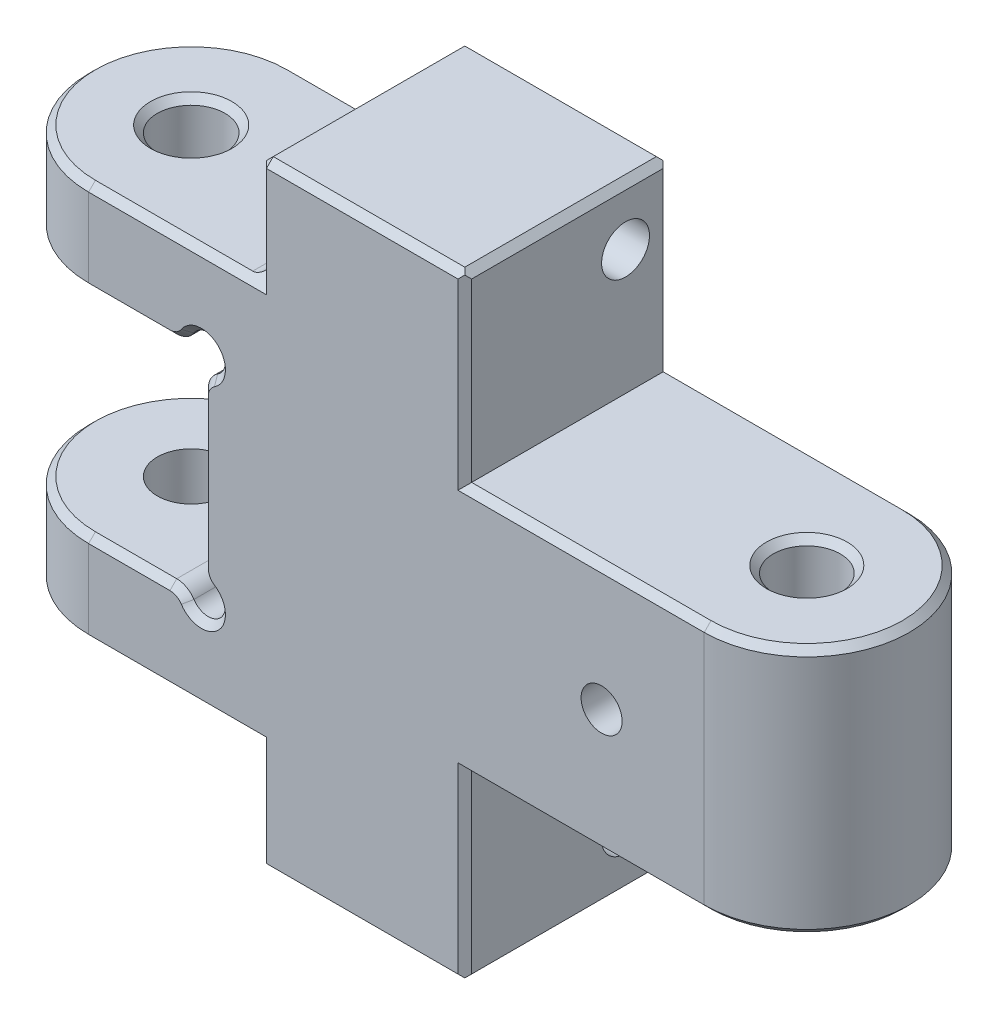
SolidWorks part; units mm, degrees
ref_plane "Front Plane" through (0, 0, 0) normal (0, 0, 1) x (1, 0, 0)
ref_plane "Top Plane" through (0, 0, 0) normal (0, 1, 0) x (1, 0, 0)
ref_plane "Right Plane" through (0, 0, 0) normal (1, 0, 0) x (0, 0, -1)
sketch "Sketch1" plane through (0, 0, 0) normal (0, 1, 0) x (1, 0, 0)
  line L0 (-4.5, 0) -> (4.5, 0) construction
  line L1 (-4.5, 1.5) -> (4.5, 1.5)
  line L2 (-4.5, -1.5) -> (4.5, -1.5)
  arc A0 (-4.5, 1.5) -> (-4.5, -1.5) centre (-4.5, 0) ccw
  arc A1 (4.5, -1.5) -> (4.5, 1.5) centre (4.5, 0) ccw
  circle A2 centre (-4.5, 0) radius 0.495
  circle A3 centre (4.5, 0) radius 0.49
  point P3 (0, 0)
  dimension "D3" = 0.99
  dimension "D4" = 0.98
  dimension "D1" = 9
  dimension "D2" = 3
extrude "Boss-Extrude1" add sketch "Sketch1" along normal mid plane 3.65
sketch "Sketch2" plane through (0, 0, 0) normal (0, -1, 0) x (1, 0, 0)
  circle A0 centre (4.5, 0) radius 0.49
  circle A1 centre (4.5, 0) radius 0.75
  circle A2 centre (4.5, 0) radius 0.49 construction
extrude "Boss-Extrude3" [suppressed] add sketch "Sketch2" along normal mid plane 3.5
sketch "Sketch3" plane through (0, 0, 0) normal (0, 1, 0) x (1, 0, 0)
  line L0 (-2, 1.5) -> (1, -1.5) construction
  line L1 (-2, -1.5) -> (1, -1.5)
  line L2 (-2, -1.5) -> (-2, 1.5)
  line L3 (-2, 1.5) -> (1, 1.5)
  line L4 (1, -1.5) -> (1, 1.5)
  line L5 (1, 1.5) -> (-2, -1.5) construction
  line L6 (4.5, 1.5) -> (-4.5, 1.5) construction
  line L7 (-4.5, -1.5) -> (4.5, -1.5) construction
  circle A0 centre (-4.5, 0) radius 0.495 construction
  point P4 (-0.5, 0)
  dimension "D1" = 4
  dimension "D2" = 3
extrude "Boss-Extrude4" add sketch "Sketch3" along normal mid plane 9
sketch "Sketch6" plane through (0, 0, -1.5) normal (0, 0, -1) x (-1, 0, 0)
  line L0 (4, 2.9) -> (4, 0) construction
  line L1 (2, 2.9) -> (6, 2.9)
  line L2 (2, 2.9) -> (2, -2.9)
  line L3 (2, -2.9) -> (6, -2.9)
  line L4 (6, 2.9) -> (6, -2.9)
  line L5 (4, 0) -> (4, -2.9) construction
  line L7 (2, -1.825) -> (2, -4.5) construction
  point P0 (4, 0)
  dimension "D1" = 5.8
  dimension "D2" = 4
extrude "Boss-Extrude5" add sketch "Sketch6" against normal up to surface (3 mm away) up to face at (-0.3333, 0, 1.5)
sketch "Sketch8" plane through (0, 0, 0) normal (0, 1, 0) x (1, 0, 0)
  circle A0 centre (-4.5, 0) radius 0.495
  point P2 (4.5, 0)
  dimension "D1" = 0.99
  dimension "D2" = 9
extrude "Cut-Extrude4" cut sketch "Sketch8" against normal mid plane 10
ref_axis "Axis2" through (-4.5, -2.9, 0) along (0, 1, 0)
sketch "Sketch7" plane through (0, 0, -1.5) normal (0, 0, -1) x (-1, 0, 0)
  line L0 (6, -2.9) -> (6, 2.9) construction
  line L1 (9.15, 1.55) -> (2.85, 1.55)
  line L2 (9.15, 1.55) -> (9.15, -1.55)
  line L3 (9.15, -1.55) -> (2.85, -1.55)
  line L4 (2.85, 1.55) -> (2.85, -1.55)
  line L8 (4.5, -2.9) -> (4.5, 2.9) construction
  point P0 (6, 0)
  point P7 (2.85, 0)
  dimension "D1" = 1.65
  dimension "D2" = 3.1
extrude "Cut-Extrude3" cut sketch "Sketch7" against normal blind 10
sketch "Sketch9" plane through (0, 0, -1.5) normal (0, 0, -1) x (-1, 0, 0)
  circle A0 centre (2.85, 1.55) radius 0.25
  circle A1 centre (2.85, -1.55) radius 0.25
  dimension "D1" = 0.5
extrude "Cut-Extrude5" cut sketch "Sketch9" against normal through all
sketch "Sketch4" plane through (-2, 0, 0) normal (-1, 0, 0) x (0, 0, 1)
  line L0 (-2.045, 0) -> (2.3084, 0) construction
  line L1 (1.65, 0) -> (-1.65, 0) construction
  line L2 (-1.5, 4.5) -> (1.5, 4.5) construction
  line L3 (-1.5, 4.5) -> (-1.5, 2.9) construction
  circle A0 centre (-0.85, 3.65) radius 0.35
  circle A1 centre (-0.85, -3.65) radius 0.35
  dimension "D1" = 0.7
  dimension "D2" = 0.85
  dimension "D3" = 0.65
extrude "Cut-Extrude1" cut sketch "Sketch4" against normal through all
ref_axis "Axis1" through (-4.5, -2.9, 0) along (0, 1, 0)
sketch "Sketch5" plane through (0, 0, 1.5) normal (0, 0, 1) x (1, 0, 0)
  line L0 (1.65, 0) -> (-1.65, 0) construction
  line L2 (-4.5, -2.9) -> (-4.5, -1.55) construction
  circle A0 centre (3, 0) radius 0.3
  dimension "D1" = 0.6
  dimension "D2" = 7.5
extrude "Cut-Extrude2" cut sketch "Sketch5" against normal blind 10
fillet "Fillet1" [suppressed] radius 0.5
fillet "Fillet3" radius 0.3 4 edges at (-3.1, -1.55, 0) (-2.85, -1.3, 0) (-3.1, 1.55, 0) (-2.85, 1.3, 0)
fillet "Fillet4" radius 1.5 4 edges at (-6, 2.225, 1.5) (-6, 2.225, -1.5) (-6, -2.225, 1.5) (-6, -2.225, -1.5)
chamfer "Chamfer1" distance 0.1 angle 45 4 edges at (4.5, -1.825, 0.49) (4.5, 1.825, 0.49) (-4.995, 2.9, 0) (-4.005, -2.9, 0)
chamfer "Chamfer2" distance 0.1 angle 45 12 edges at (2.75, 1.825, 1.5) (6, 1.825, 0) (1, 3.1625, 1.5) (1, 4.5, 0) (1, 3.1625, -1.5) (2.75, 1.825, -1.5) (2.75, -1.825, 1.5) (6, -1.825, 0) (1, -3.1625, 1.5) (1, -4.5, 0) (1, -3.1625, -1.5) (2.75, -1.825, -1.5)
chamfer "Chamfer3" distance 0.1 angle 45 30 edges at (-3.25, -2.9, 1.5) (-5.5607, -2.9, 1.0607) (-5.5607, -2.9, -1.0607) (-3.25, -2.9, -1.5) (-3.25, 2.9, 1.5) (-5.5607, 2.9, 1.0607) (-5.5607, 2.9, -1.0607) (-3.25, 2.9, -1.5) (-5.5607, 1.55, 1.0607) (-3.9055, 1.55, 1.5) (-5.5607, 1.55, -1.0607) (-3.168, 1.5863, 1.5) (-3.9055, 1.55, -1.5) (-2.6732, 1.7268, 1.5) (-3.168, 1.5863, -1.5) (-2.8137, 1.232, 1.5) (-2.6732, 1.7268, -1.5) (-2.85, 0, 1.5) (-2.8137, 1.232, -1.5) (-2.8137, -1.232, 1.5) (-2.85, 0, -1.5) (-2.6732, -1.7268, 1.5) (-2.8137, -1.232, -1.5) (-3.168, -1.5863, 1.5) (-2.6732, -1.7268, -1.5) (-3.9055, -1.55, 1.5) (-3.168, -1.5863, -1.5) (-5.5607, -1.55, 1.0607) (-3.9055, -1.55, -1.5) (-5.5607, -1.55, -1.0607)
chamfer "Chamfer4" distance 0.1 angle 45 10 edges at (-2, 3.65, 1.5) (-0.55, 4.5, 1.5) (-2, 4.5, 0) (-0.55, 4.5, -1.5) (-2, 3.65, -1.5) (-0.55, -4.5, 1.5) (-0.55, -4.5, -1.5) (-2, -3.65, 1.5) (-2, -4.5, 0) (-2, -3.65, -1.5)
fillet "Fillet5" radius 0.2 2 edges at (-2, -2.9, 0) (-2, 2.9, 0)
